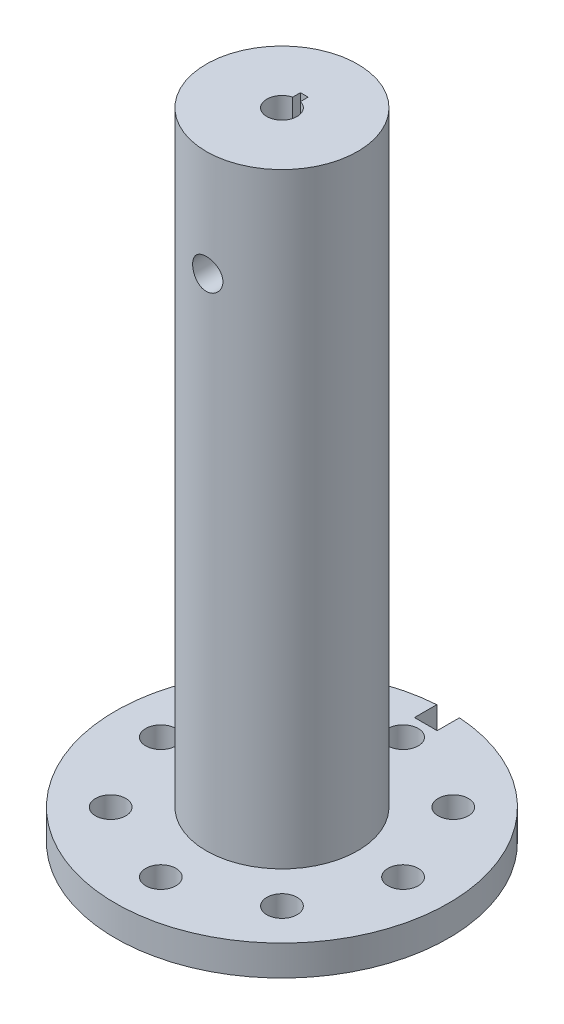
SolidWorks part; units mm, degrees
ref_plane "Front Plane" through (0, 0, 0) normal (0, 0, 1) x (1, 0, 0)
ref_plane "Top Plane" through (0, 0, 0) normal (0, 1, 0) x (1, 0, 0)
ref_plane "Right Plane" through (0, 0, 0) normal (1, 0, 0) x (0, 0, -1)
sketch "Sketch1" plane through (0, 0, 0) normal (0, 1, 0) x (1, 0, 0)
  circle A0 centre (0, 0) radius 11
  circle A1 centre (0, 8) radius 1
  circle A2 centre (5.6569, 5.6569) radius 1
  circle A3 centre (8, 0) radius 1
  circle A4 centre (5.6569, -5.6569) radius 1
  circle A5 centre (0, -8) radius 1
  circle A6 centre (-5.6569, -5.6569) radius 1
  circle A7 centre (-8, 0) radius 1
  circle A8 centre (-5.6569, 5.6569) radius 1
  point P22 (0, 0)
  dimension "D1" = 22
  dimension "D2" = 2
  dimension "D6" = 8
  dimension "D3" = 8
  dimension "D5" = 8
  dimension "D4" = 8
extrude "Boss-Extrude1" add sketch "Sketch1" along normal blind 2
sketch "Sketch2" plane through (0, 2, 0) normal (0, 1, 0) x (1, 0, 0)
  circle A0 centre (0, 0) radius 3.5
  dimension "D1" = 7
extrude "Cut-Extrude1" cut sketch "Sketch2" against normal through all
ref_plane "Plane1" through (0, 0, 0) normal (0, 1, 0) x (1, 0, 0)
sketch "Sketch3" plane through (0, 0, 0) normal (0, 1, 0) x (1, 0, 0)
  circle A0 centre (0, 0) radius 5
  circle A1 centre (0, 0) radius 11
  dimension "D1" = 10
  dimension "D2" = 22
sketch "Sketch4" plane through (0, 2, 0) normal (0, 1, 0) x (1, 0, 0)
  line L1 (-0.75, 12.5) -> (0.75, 12.5)
  line L2 (-0.75, 12.5) -> (-0.75, 9.5)
  line L3 (-0.75, 9.5) -> (0.75, 9.5)
  line L4 (0.75, 12.5) -> (0.75, 9.5)
  line L5 (-0.75, 12.5) -> (0.75, 9.5) construction
  line L6 (-0.75, 9.5) -> (0.75, 12.5) construction
  circle A0 centre (0, 0) radius 11 construction
  point P0 (0, 11)
  dimension "D1" = 1.5
  dimension "D2" = 3
extrude "Cut-Extrude3" cut sketch "Sketch4" against normal blind 4
sketch "Sketch5" plane through (0, 2, 0) normal (0, 1, 0) x (1, 0, 0)
  circle A0 centre (0, 0) radius 3.5
  circle A1 centre (0, 0) radius 5
  dimension "D1" = 7
  dimension "D2" = 10
extrude "Boss-Extrude2" add sketch "Sketch5" along normal blind 20 contours A1 | A0
sketch "Sketch6" plane through (0, 22, 0) normal (0, 1, 0) x (1, 0, 0)
  line L0 (-0.255, 0.9669) -> (0.255, 0.9669)
  line L1 (-0.255, 0.9669) -> (-0.255, 1.4769)
  line L2 (0.255, 0.9669) -> (0.255, 1.4769)
  line L3 (-0.255, 1.4769) -> (0.255, 1.4769)
  circle A0 centre (0, 0) radius 1
  circle A1 centre (0, 0) radius 3.5
  circle A2 centre (0, 0) radius 5
  circle M4 centre (0, 0) radius 5
  circle M5 centre (0, 0) radius 3.5
  dimension "D1" = 2
  dimension "D4" = 7
  dimension "D5" = 10
  dimension "D2" = 0.51
  dimension "D3" = 0.51
extrude "Boss-Extrude3" add sketch "Sketch6" along normal blind 20 contours A0 L1 L3 L2 M5 | M4 M5 region at (-3.401, 22, 0) region at (-4.8586, 22, 0)
sketch "Sketch7" plane through (0, 0, 0) normal (0, 0, 1) x (1, 0, 0)
  line L0 (11, 0) -> (-11, 0) construction
  circle A0 centre (0, 35) radius 1
  point P4 (-0.7233, 30)
  point P5 (0, 30)
  point P6 (0, 0)
  dimension "D1" = 2
  dimension "D2" = 35
extrude "Cut-Extrude4" cut sketch "Sketch7" against normal blind 1 and the other way blind 5
